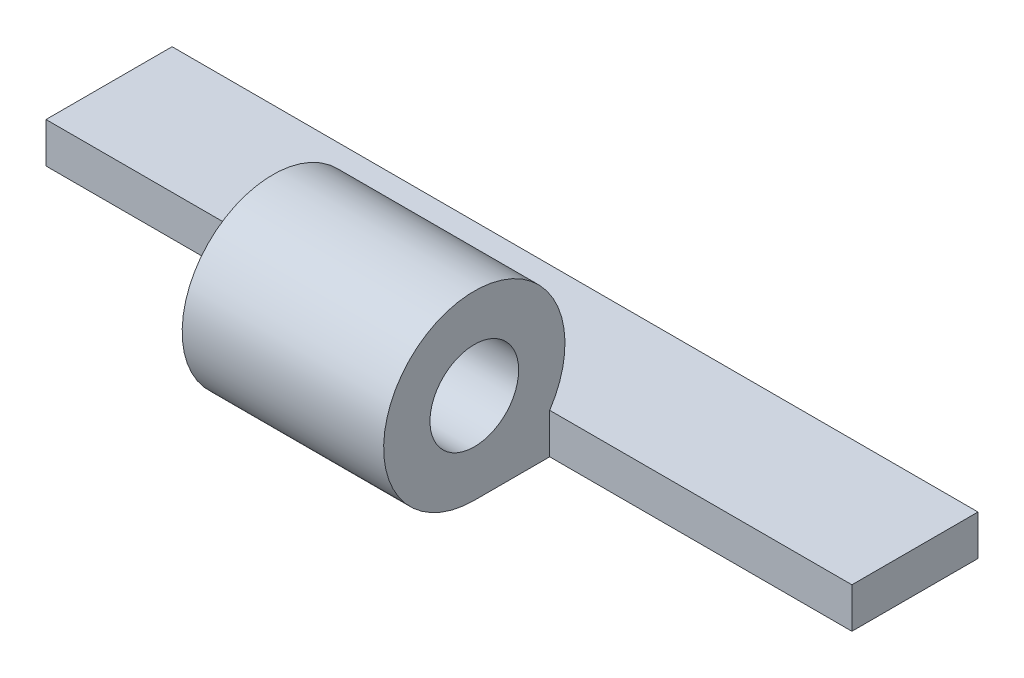
SolidWorks part; units mm, degrees
ref_plane "Ebene vorne" through (0, 0, 0) normal (0, 0, 1) x (1, 0, 0)
ref_plane "Ebene oben" through (0, 0, 0) normal (0, 1, 0) x (1, 0, 0)
ref_plane "Ebene rechts" through (0, 0, 0) normal (1, 0, 0) x (0, 0, -1)
sketch "Skizze2" plane through (0, 0, 0) normal (0, 1, 0) x (1, 0, 0)
  line L1 (-7.5, 2.5) -> (7.5, 2.5)
  line L2 (-7.5, 2.5) -> (-7.5, -2.5)
  line L3 (-7.5, -2.5) -> (7.5, -2.5)
  line L4 (7.5, 2.5) -> (7.5, -2.5)
  line L5 (-7.5, 2.5) -> (7.5, -2.5) construction
  line L6 (-7.5, -2.5) -> (7.5, 2.5) construction
  point P0 (0, 0)
  dimension "D1" = 15
  dimension "D2" = 5
extrude "Aufsatz-Linear austragen1" add sketch "Skizze2" along normal blind 1
sketch "Skizze3" plane through (7.5, 0, 0) normal (1, 0, 0) x (0, 0, -1)
  circle A0 centre (-2.5, 2.25) radius 2.25
  circle A1 centre (-2.5, 2.25) radius 1.1
  dimension "D1" = 2.2
  dimension "D2" = 4.5
extrude "Aufsatz-Linear austragen2" add sketch "Skizze3" against normal up to surface (15 mm away) up to face at (-7.5, 0.5, 0)
ref_plane "Tangential Ebene" through (0, 0, 0.25) normal (0, 0, -1) x (-1, 0, 0)
sketch "Skizze5" plane through (7.5, 0, 0) normal (1, 0, 0) x (0, 0, -1)
  line L0 (-0.6292, 1) -> (-0.6292, 0)
  line L1 (-0.6292, 0) -> (-2.5, 0)
  line L3 (2.5, 1) -> (-0.6292, 1)
  line L4 (-2.5, 0) -> (2.5, 0)
  line L5 (2.5, 0) -> (2.5, 1)
  line L6 (2.5, 1) -> (-0.6292, 1) construction
  line L7 (-2.5, 0) -> (2.5, 0) construction
  line L8 (2.5, 0) -> (2.5, 1) construction
  arc A1 (-0.6292, 1) -> (-2.5, 0) centre (-2.5, 2.25) ccw
  arc A2 (-0.6292, 1) -> (-2.5, 0) centre (-2.5, 2.25) ccw
  dimension "D1" = 0
extrude "Schnitt-Linear austragen1" cut sketch "Skizze5" against normal blind 5
pattern_linear "Lineares Muster1" count 2 spacing 10 along (-1, 0, 0) of "Schnitt-Linear austragen1"
ref_plane "Spiegelebene" through (0, 0, 0) normal (1, 0, 0) x (0, 0, -1)
sketch "Skizze7" plane through (7.5, 0, 0) normal (1, 0, 0) x (0, 0, -1)
  line L1 (2.5, 1) -> (-0.6292, 1)
  line L2 (2.5, 1) -> (2.5, 0)
  line L3 (2.5, 0) -> (-0.6292, 0)
  line L4 (-0.6292, 1) -> (-0.6292, 0)
extrude "Verbreiterung" add sketch "Skizze7" along normal blind 2.5
mirror "Spiegeln1" about plane through (0, 0, 0) normal (1, 0, 0) of "Verbreiterung"
ref_axis "Achse1" through (-2.5, 2.25, 2.5) along (1, 0, 0)
